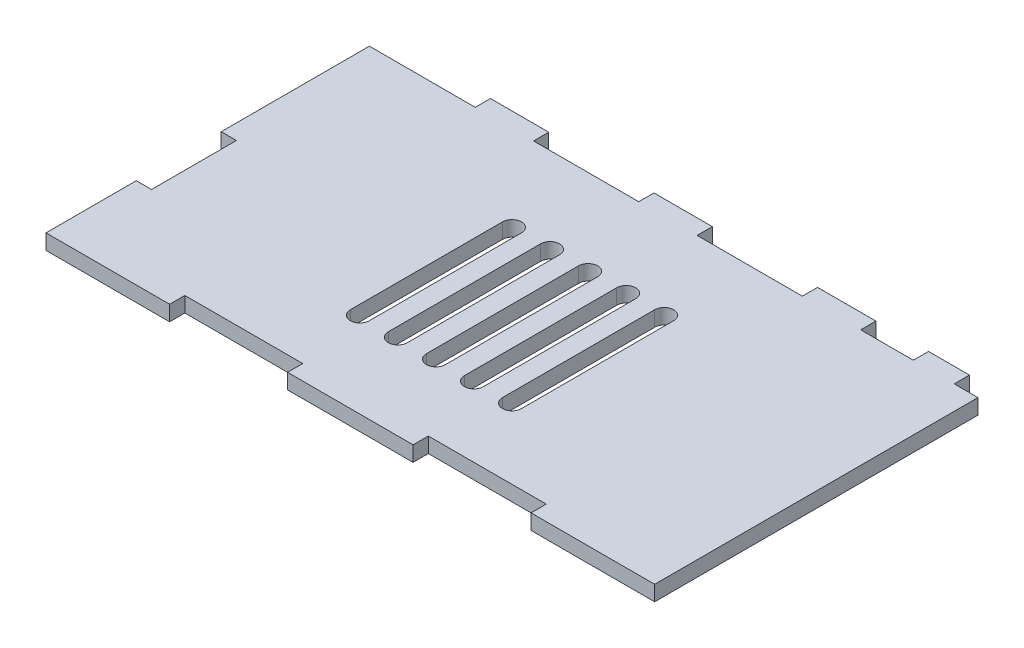
SolidWorks part; units mm, degrees
ref_plane "Front Plane" through (0, 0, 0) normal (0, 0, 1) x (1, 0, 0)
ref_plane "Top Plane" through (0, 0, 0) normal (0, 1, 0) x (1, 0, 0)
ref_plane "Right Plane" through (0, 0, 0) normal (1, 0, 0) x (0, 0, -1)
sketch "Sketch1" plane through (0, 0, 0) normal (0, 1, 0) x (1, 0, 0)
  line L1 (0, 0) -> (156, 0)
  line L2 (0, 0) -> (0, 85)
  line L3 (0, 85) -> (156, 85)
  line L4 (156, 0) -> (156, 85)
  dimension "D1" = 156
  dimension "D2" = 85
extrude "Boss-Extrude1" add sketch "Sketch1" along normal blind 4
sketch "Sketch2" plane through (0, 4, 0) normal (0, 1, 0) x (1, 0, 0)
  line L0 (156, 85) -> (0, 85) construction
  line L1 (23.83, 85) -> (39.16, 85)
  line L2 (23.83, 85) -> (23.83, 89)
  line L3 (23.83, 89) -> (39.16, 89)
  line L4 (39.16, 85) -> (39.16, 89)
  line L5 (0, 85) -> (0, 0) construction
  line L6 (66.83, 85) -> (66.83, 89)
  line L7 (66.83, 85) -> (82.16, 85)
  line L8 (82.16, 85) -> (82.16, 89)
  line L9 (66.83, 89) -> (82.16, 89)
  line L10 (109.83, 85) -> (109.83, 89)
  line L11 (109.83, 85) -> (125.16, 85)
  line L12 (125.16, 85) -> (125.16, 89)
  line L13 (109.83, 89) -> (125.16, 89)
  dimension "D1" = 23.83
  dimension "D2" = 15.33
  dimension "D3" = 4
extrude "Boss-Extrude2" add sketch "Sketch2" against normal blind 4
sketch "Sketch3" plane through (0, 4, 0) normal (0, 1, 0) x (1, 0, 0)
  line L0 (59.5, 0) -> (59.5, 4)
  line L1 (123.5, 0) -> (92.5, 0)
  line L2 (123.5, 0) -> (123.5, 4)
  line L3 (123.5, 4) -> (92.5, 4)
  line L4 (92.5, 0) -> (92.5, 4)
  line L5 (59.5, 0) -> (28.5, 0)
  line L6 (28.5, 0) -> (28.5, 4)
  line L7 (59.5, 4) -> (28.5, 4)
  line L12 (-4.5, 0) -> (-4.5, 4) [skipped]
  line L13 (-4.5, 0) -> (-35.5, 0) [skipped]
  line L14 (-35.5, 0) -> (-35.5, 4) [skipped]
  line L15 (-4.5, 4) -> (-35.5, 4) [skipped]
  line L16 (0, 0) -> (156, 0) construction
  dimension "D1" = 31
  dimension "D2" = 4
  dimension "D4" = 32.5
  dimension "D3" = 3
extrude "Cut-Extrude2" cut sketch "Sketch3" against normal blind 4
sketch "Sketch4" plane through (0, 4, 0) normal (0, 1, 0) x (1, 0, 0)
  line L0 (0, 85) -> (0, 0) construction
  line L1 (0, 0) -> (-4, 0)
  line L2 (0, 0) -> (0, 26.74)
  line L3 (0, 26.74) -> (-4, 26.74)
  line L4 (-4, 0) -> (-4, 26.74)
  line L5 (0, 47.98) -> (-4, 47.98)
  line L6 (0, 47.98) -> (0, 76.22)
  line L7 (0, 76.22) -> (-4, 76.22)
  line L8 (-4, 47.98) -> (-4, 76.22)
  dimension "D2" = 4
  dimension "D1" = 26.74
  dimension "D3" = 21.24
  dimension "D4" = 4
  dimension "D5" = 28.24
extrude "Boss-Extrude3" add sketch "Sketch4" against normal blind 4
sketch "Sketch5" plane through (0, 4, 0) normal (0, 1, 0) x (1, 0, 0)
  line L0 (156, 85) -> (125.16, 85) construction
  line L1 (149.75, 85) -> (139, 85)
  line L2 (149.75, 85) -> (149.75, 89)
  line L3 (149.75, 89) -> (139, 89)
  line L4 (139, 85) -> (139, 89)
  line L5 (156, 0) -> (156, 85) construction
  dimension "D1" = 6.25
  dimension "D2" = 10.75
  dimension "D3" = 4
extrude "Boss-Extrude4" add sketch "Sketch5" against normal blind 4
sketch "Sketch6" plane through (0, 4, 0) normal (0, 1, 0) x (1, 0, 0)
  line L0 (76, 22.5) -> (76, 62.5) construction
  line L1 (73.5, 22.5) -> (73.5, 62.5)
  line L2 (78.5, 22.5) -> (78.5, 62.5)
  line L3 (156, 0) -> (156, 85) construction
  line L4 (59.5, 0) -> (92.5, 0) construction
  line L5 (68.5, 22.5) -> (68.5, 62.5)
  line L6 (63.5, 22.5) -> (63.5, 62.5)
  line L7 (66, 22.5) -> (66, 62.5) construction
  line L8 (58.5, 22.5) -> (58.5, 62.5)
  line L9 (53.5, 22.5) -> (53.5, 62.5)
  line L10 (56, 22.5) -> (56, 62.5) construction
  line L11 (78.5, 22.5) -> (78.5, 62.5)
  line L12 (73.5, 22.5) -> (73.5, 62.5)
  line L13 (76, 22.5) -> (76, 62.5) construction
  line L14 (68.5, 22.5) -> (68.5, 62.5)
  line L15 (63.5, 22.5) -> (63.5, 62.5)
  line L16 (66, 22.5) -> (66, 62.5) construction
  line L17 (88.5, 22.5) -> (88.5, 62.5)
  line L18 (83.5, 22.5) -> (83.5, 62.5)
  line L19 (86, 22.5) -> (86, 62.5) construction
  line L20 (78.5, 22.5) -> (78.5, 62.5)
  line L21 (73.5, 22.5) -> (73.5, 62.5)
  line L22 (76, 22.5) -> (76, 62.5) construction
  line L23 (88.5, 22.5) -> (88.5, 62.5)
  line L24 (83.5, 22.5) -> (83.5, 62.5)
  line L25 (86, 22.5) -> (86, 62.5) construction
  line L26 (98.5, 22.5) -> (98.5, 62.5)
  line L27 (93.5, 22.5) -> (93.5, 62.5)
  line L28 (96, 22.5) -> (96, 62.5) construction
  arc A0 (73.5, 22.5) -> (78.5, 22.5) centre (76, 22.5) ccw
  arc A1 (78.5, 62.5) -> (73.5, 62.5) centre (76, 62.5) ccw
  arc A2 (63.5, 22.5) -> (68.5, 22.5) centre (66, 22.5) ccw
  arc A3 (68.5, 62.5) -> (63.5, 62.5) centre (66, 62.5) ccw
  arc A4 (53.5, 22.5) -> (58.5, 22.5) centre (56, 22.5) ccw
  arc A5 (58.5, 62.5) -> (53.5, 62.5) centre (56, 62.5) ccw
  arc A6 (73.5, 22.5) -> (78.5, 22.5) centre (76, 22.5) ccw
  arc A7 (78.5, 62.5) -> (73.5, 62.5) centre (76, 62.5) ccw
  arc A8 (63.5, 22.5) -> (68.5, 22.5) centre (66, 22.5) ccw
  arc A9 (68.5, 62.5) -> (63.5, 62.5) centre (66, 62.5) ccw
  arc A10 (83.5, 22.5) -> (88.5, 22.5) centre (86, 22.5) ccw
  arc A11 (88.5, 62.5) -> (83.5, 62.5) centre (86, 62.5) ccw
  arc A12 (73.5, 22.5) -> (78.5, 22.5) centre (76, 22.5) ccw
  arc A13 (78.5, 62.5) -> (73.5, 62.5) centre (76, 62.5) ccw
  arc A14 (83.5, 22.5) -> (88.5, 22.5) centre (86, 22.5) ccw
  arc A15 (88.5, 62.5) -> (83.5, 62.5) centre (86, 62.5) ccw
  arc A16 (93.5, 22.5) -> (98.5, 22.5) centre (96, 22.5) ccw
  arc A17 (98.5, 62.5) -> (93.5, 62.5) centre (96, 62.5) ccw
  point P2 (76, 42.5)
  point P9 (156, 42.5)
  point P18 (66, 42.5)
  point P25 (56, 42.5)
  point P32 (76, 42.5)
  point P39 (66, 42.5)
  point P46 (86, 42.5)
  point P53 (76, 42.5)
  point P60 (86, 42.5)
  point P67 (96, 42.5)
  dimension "D1" = 5
  dimension "D2" = 40
  dimension "D3" = 3
  dimension "D4" = 3
extrude "Cut-Extrude3" cut sketch "Sketch6" against normal blind 4 contours L5 A3 L6 A2 | L8 A5 L9 A4 | L2 A1 L1 A0 | L17 A11 L18 A10 | L26 A17 L27 A16 region at (76, 4, -42.5) region at (66, 4, -42.5) region at (56, 4, -42.5) region at (86, 4, -42.5) region at (96, 4, -42.5)
sketch "Sketch7" plane through (0, 4, 0) normal (0, 1, 0) x (1, 0, 0)
  line L1 (0, 85) -> (-4, 85)
  line L2 (0, 85) -> (0, 76.22)
  line L3 (0, 76.22) -> (-4, 76.22)
  line L4 (-4, 85) -> (-4, 76.22)
  line L5 (0, 47.98) -> (-4, 47.98)
  line L6 (0, 47.98) -> (0, 46.0568)
  line L7 (0, 46.0568) -> (-4, 46.0568)
  line L8 (-4, 47.98) -> (-4, 46.0568)
extrude "Boss-Extrude5" add sketch "Sketch7" against normal blind 4
sketch "Sketch8" plane through (0, 4, 0) normal (0, 1, 0) x (1, 0, 0)
  line L0 (0.5, 23.7401) -> (-3.5, 23.7401) construction
  line L1 (-4, 26.74) -> (0, 26.74)
  line L2 (-4, 26.74) -> (-4, 23.7401)
  line L3 (-4, 23.7401) -> (0, 23.7401)
  line L4 (0, 26.74) -> (0, 23.7401)
extrude "Cut-Extrude4" cut sketch "Sketch8" against normal blind 4
equation "\"Tolerantie\"= 0.5"
equation "\"D1@Sketch2\"=24.33-\"Tolerantie\""
equation "\"D2@Sketch2\"=14.33+2*\"Tolerantie\""
equation "\"D4@Sketch3\"=32+\"Tolerantie\""
equation "\"D1@Sketch3\"=32-2*\"Tolerantie\""
equation "\"D1@Sketch4\"=26.24+\"Tolerantie\""
equation "\"D3@Sketch4\"=22.24-2*\"Tolerantie\""
equation "\"D5@Sketch4\"=27.24+2*\"Tolerantie\""
